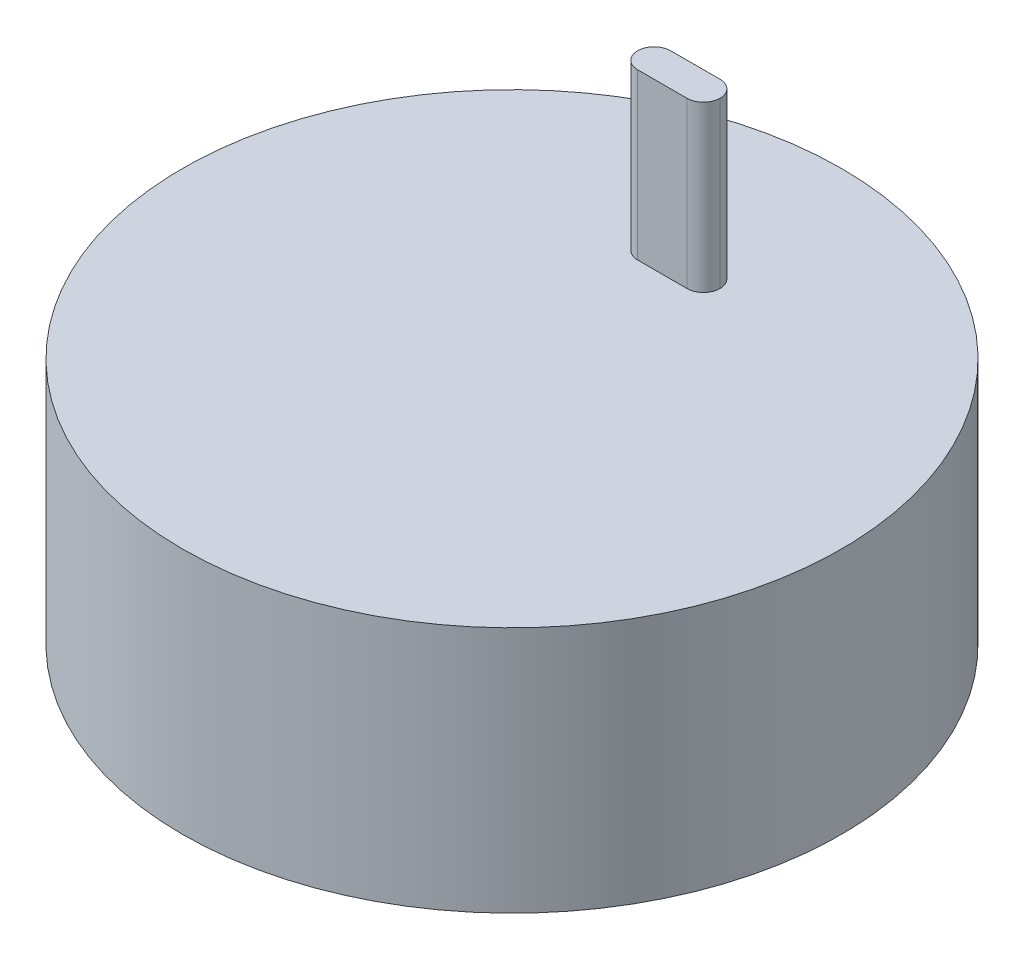
SolidWorks part; units mm, degrees
ref_plane "Front Plane" through (0, 0, 0) normal (0, 0, 1) x (1, 0, 0)
ref_plane "Top Plane" through (0, 0, 0) normal (0, 1, 0) x (1, 0, 0)
ref_plane "Right Plane" through (0, 0, 0) normal (1, 0, 0) x (0, 0, -1)
sketch "Sketch1" plane through (0, 0, 0) normal (0, 1, 0) x (1, 0, 0)
  circle A0 centre (0, 0) radius 20
  point P3 (0, 0)
extrude "Boss-Extrude1" add sketch "Sketch1" along normal blind 15 contours A0
sketch "Sketch2" plane through (0, 15, 0) normal (0, 1, 0) x (1, 0, 0)
  line L0 (0, 0) -> (0.1253, 10) construction
  line L1 (2.6253, 11) -> (-2.3747, 11)
  line L2 (2.6253, 11) -> (2.6253, 9)
  line L3 (2.6253, 9) -> (-2.3747, 9)
  line L4 (-2.3747, 11) -> (-2.3747, 9)
  line L5 (2.6253, 11) -> (-2.3747, 9) construction
  line L6 (2.6253, 9) -> (-2.3747, 11) construction
  point P0 (0.1253, 10)
  dimension "D1" = 2
  dimension "D2" = 5
  dimension "D3" = 10
extrude "Boss-Extrude2" add sketch "Sketch2" along normal blind 10
fillet "Fillet1" radius 1 4 edges at (-2.3747, 20, -11) (2.6253, 20, -11) (-2.3747, 20, -9) (2.6253, 20, -9)
